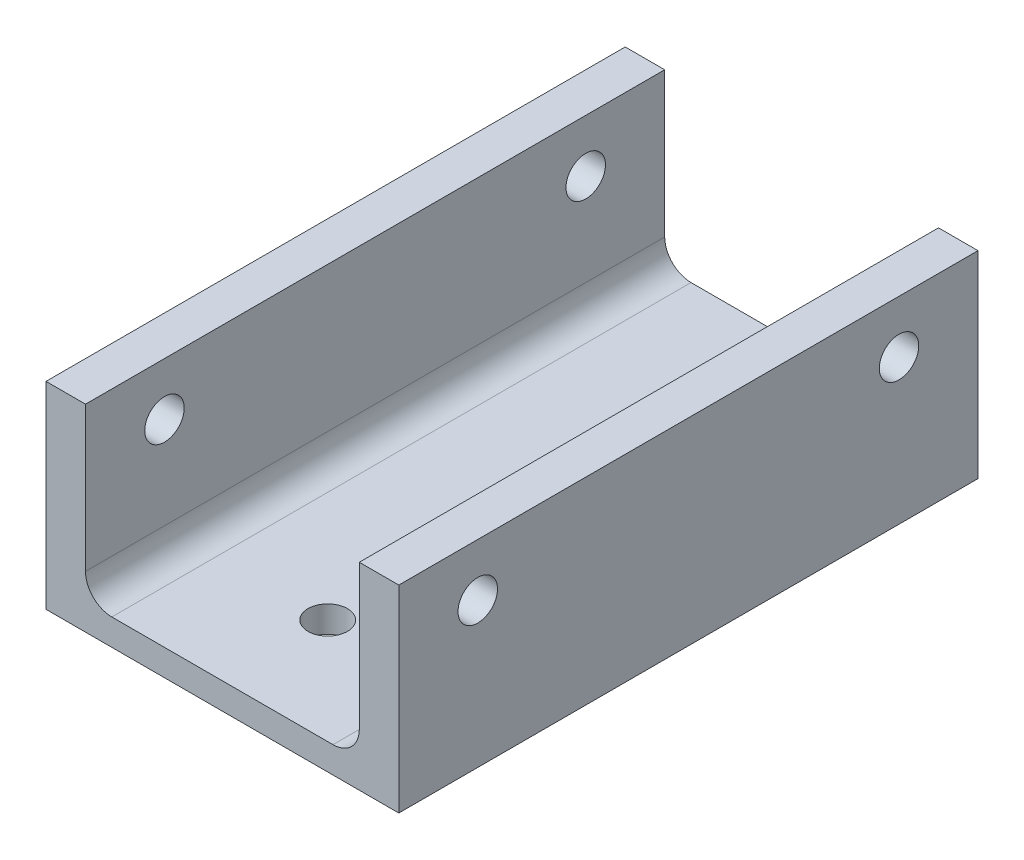
SolidWorks part; units mm, degrees
ref_plane "Front Plane" through (0, 0, 0) normal (0, 0, 1) x (1, 0, 0)
ref_plane "Top Plane" through (0, 0, 0) normal (0, 1, 0) x (1, 0, 0)
ref_plane "Right Plane" through (0, 0, 0) normal (1, 0, 0) x (0, 0, -1)
sketch "Sketch2" plane through (0, 0, 0) normal (0, 0, 1) x (1, 0, 0)
  line L0 (23.8, 15) -> (26.8, 15)
  line L1 (0, 0) -> (26.8, 0)
  line L2 (0, 0) -> (0, 15)
  line L3 (0, 15) -> (3, 15)
  line L4 (26.8, 0) -> (26.8, 15)
  line L6 (3, 15) -> (3, 2)
  line L7 (3, 2) -> (23.8, 2)
  line L8 (23.8, 15) -> (23.8, 2)
  dimension "D1" = 3
  dimension "D2" = 15
  dimension "D3" = 2
  dimension "D4" = 26.8
extrude "Boss-Extrude1" add sketch "Sketch2" along normal blind 44
fillet "Fillet1" radius 2 2 edges at (23.8, 2, 22) (3, 2, 22)
sketch "Sketch3" plane through (0, 0, 0) normal (0, -1, 0) x (1, 0, 0)
  line L0 (0, 44) -> (26.8, 44) construction
  line L1 (0, 0) -> (26.8, 0) construction
  line L2 (26.8, 44) -> (26.8, 0) construction
  circle A0 centre (13.4, 36) radius 1.5
  circle A1 centre (13.4, 8) radius 1.5
  dimension "D1" = 3
  dimension "D2" = 8
  dimension "D3" = 8
  dimension "D4" = 13.4
extrude "Cut-Extrude1" cut sketch "Sketch3" against normal blind 30
sketch "Sketch4" plane through (0, 0, 0) normal (-1, 0, 0) x (0, 0, 1)
  line L0 (44, 15) -> (0, 15) construction
  line L1 (0, 15) -> (0, 0) construction
  line L2 (44, 15) -> (44, 0) construction
  circle A0 centre (6, 11) radius 1.5
  circle A1 centre (38, 11) radius 1.5
  dimension "D1" = 3
  dimension "D4" = 6
  dimension "D5" = 6
  dimension "D2" = 4
  dimension "D3" = 4
extrude "Cut-Extrude2" cut sketch "Sketch4" against normal blind 30
